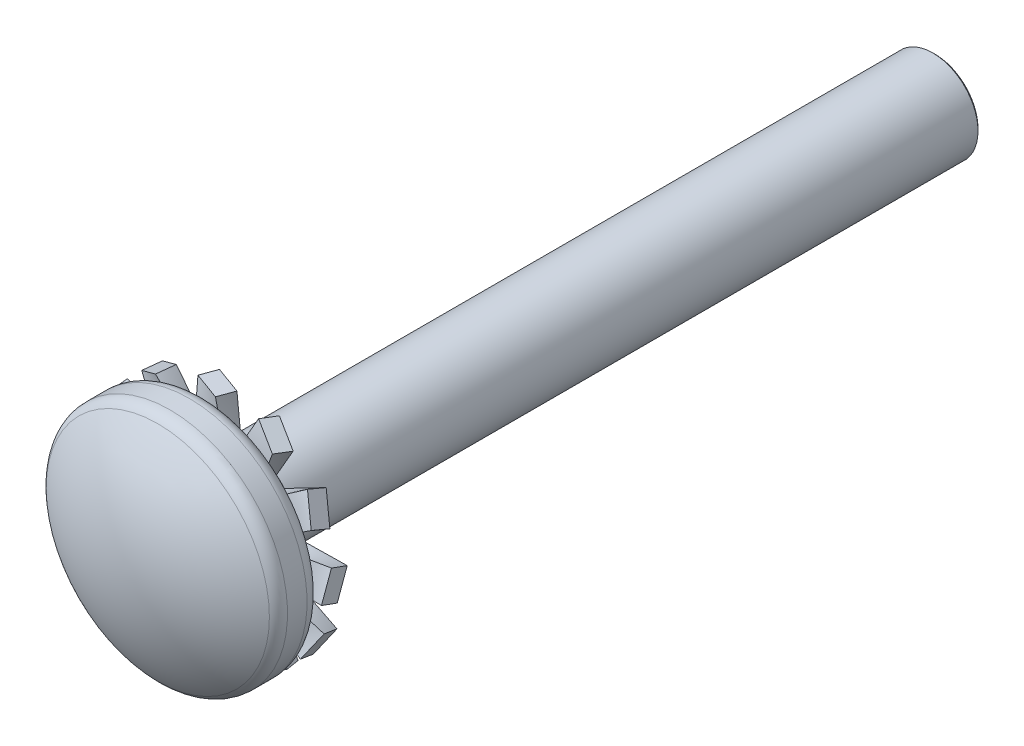
SolidWorks part; units mm, degrees
material "AISI 304"
ref_plane "Front Plane" through (0, 0, 0) normal (0, 0, 1) x (1, 0, 0)
ref_plane "Top Plane" through (0, 0, 0) normal (0, 1, 0) x (1, 0, 0)
ref_plane "Right Plane" through (0, 0, 0) normal (1, 0, 0) x (0, 0, -1)
sketch "Sketch1" plane through (0, 0, 0) normal (0, 0, 1) x (1, 0, 0)
  circle A0 centre (0, 0) radius 2.0828
  dimension "decimal equ" = 4.1656
curve "Helix/Spiral1" pitch 0.7937 height 26.1937 turns 33 parameters "helix length"=26.1937, "pitch"=0.7937
sketch "Sketch2" plane through (0, 0, 0) normal (1, 0, 0) x (0, 0, -1)
  line L0 (0.2977, 2.0828) -> (0.3969, 2.0828)
  line L1 (0.3969, 2.0828) -> (0.6945, 1.5672)
  line L2 (0.2977, 2.0828) -> (0, 1.5672)
  line L3 (0, 1.5672) -> (0.6945, 1.5672)
  line L4 (0.3473, 2.0828) -> (0.3473, 1.5672) construction
  line L6 (0.1488, 1.825) -> (0.5457, 1.825) construction
  line L7 (0, 1.5672) -> (0, 2.0828) construction
  line L8 (0, 2.0828) -> (0, -2.0828) construction
  line L9 (0, 2.0828) -> (0, -2.0828) construction
  point P8 (-3.2742, -2.0828)
  dimension "D1" = 60
  dimension "D3" = 0.0992
  dimension "D4" = 0.3969
  dimension "D2" = 3.2742
sketch "Sketch3" plane through (0, 0, 0) normal (1, 0, 0) x (0, 0, -1)
  line L0 (0, 0) -> (-25.4, 0) construction
  line L1 (0, 1.5672) -> (0.6945, 1.5672) construction
  line L2 (0, 0) -> (-25.4, 0)
  line L3 (0, 0) -> (0, 1.5672)
  line L4 (0, 1.5672) -> (-25.4, 1.5672)
  line L5 (-25.4, 0) -> (-25.4, 1.5672)
  dimension "length" = 25.4
revolve "Revolve1" add sketch "Sketch3" angle 360 about L0
sweep "Sweep1" [suppressed] add profiles "Sketch2" path "Helix/Spiral1"
sketch "Sketch39" plane through (0, 0, 0) normal (0, 0, -1) x (-1, 0, 0)
  circle A0 centre (0, 0) radius 2.0828 construction
  circle A1 centre (0, 0) radius 2.0828
extrude "Extrude5" [suppressed] cut sketch "Sketch39" along normal through all
sketch "Sketch38" plane through (0, 0, 0) normal (0, 0, -1) x (-1, 0, 0)
  circle A2 centre (0, 0) radius 1.4875
  circle A3 centre (0, 0) radius 1.4875
extrude "Extrude6" cut sketch "Sketch38" against normal through all draft 45 flip side to cut
sketch "Sketch10" plane through (0, 0, 0) normal (1, 0, 0) x (0, 0, -1)
  line L0 (0, 0) -> (23.0169, 0) construction
  line L1 (-279.4, 12.7) -> (-25.4, 12.7)
  line L2 (-279.4, 12.7) -> (-279.4, 0)
  line L3 (-279.4, 0) -> (-25.4, 0)
  line L4 (-25.4, 12.7) -> (-25.4, 0)
  line L5 (-25.4, 0) -> (-25.4, 1.5672) construction
  dimension "D1" = 254
  dimension "D2" = 12.7
revolve "Cut-Revolve2" [suppressed] cut sketch "Sketch10" angle 360 about L0
sketch "Sketch41" plane through (0, 0, 0) normal (1, 0, 0) x (0, 0, -1)
  line L0 (-25.4, 2.0828) -> (-25.4, 1.5672)
  line L1 (-25.4, 1.5672) -> (-24.5237, 1.5672)
  line L2 (-24.5237, 1.5672) -> (-24.0081, 2.0828)
  line L3 (-25.4, 2.0828) -> (-24.0081, 2.0828)
  line L4 (0, 1.5672) -> (0.6945, 1.5672) construction
  dimension "D1" = 0.8763
  dimension "D2" = 45
revolve "Cut-Revolve4" [suppressed] cut sketch "Sketch41" angle 360 about L2
sketch "Sketch8" plane through (0, 0, 0) normal (1, 0, 0) x (0, 0, -1)
  line L0 (0, 0) -> (-6.2449, 0) construction
  line L1 (-28.321, 0) -> (-25.4, 0)
  line L2 (-28.321, 0) -> (-28.321, 4.0894)
  line L3 (-28.321, 4.0894) -> (-25.4, 4.0894)
  line L4 (-25.4, 0) -> (-25.4, 4.0894)
  line L5 (-28.321, -4.0894) -> (-25.4, -4.0894) construction
  line L6 (-25.4, 0) -> (-25.4, 1.5672) construction
  dimension "head dia" = 8.1788
  dimension "head height" = 2.921
revolve "Revolve2" add sketch "Sketch8" angle 360 about L0
sketch "Sketch11" plane through (0, 0, 0) normal (1, 0, 0) x (0, 0, -1)
  line L0 (-26.8605, 4.0894) -> (-26.8605, -4.0894) construction
  line L1 (-28.321, 0) -> (-6.8951, 0) construction
  line L2 (-28.321, 4.0894) -> (-25.4, 4.0894) construction
  line L3 (-28.321, 0) -> (-28.321, 4.0894) construction
  line L4 (-26.6049, 4.0894) -> (-25.9258, 4.0894)
  line L6 (-25.4, 0) -> (-25.4, 4.0894) construction
  line L7 (-25.4, 3.5636) -> (-24.765, 3.5636)
  line L8 (-24.765, 3.5636) -> (-24.765, 4.7244)
  line L9 (-24.765, 4.7244) -> (-28.956, 4.7244)
  line L10 (-28.956, 4.7244) -> (-28.956, 0)
  line L11 (-28.956, 0) -> (-28.321, 0)
  arc A0 (-27.0251, 3.8796) -> (-28.321, 0) centre (-21.8656, 0) ccw
  arc A1 (-25.4, 3.5636) -> (-25.9258, 4.0894) centre (-25.9258, 3.5636) ccw
  arc A2 (-27.0251, 3.8796) -> (-26.6049, 4.0894) centre (-26.6049, 3.5636) cw
  dimension "D1" = 0.5258
  dimension "D2" = 0.635
  dimension "D3" = 0.635
  dimension "D4" = 0.635
revolve "Cut-Revolve3" cut sketch "Sketch11" angle 360 about L1
ref_plane "Plane1" through (0, 0, 28.321) normal (0, 0, 1) x (1, 0, 0)
sketch "Sketch12" plane through (0, 0, 28.321) normal (0, 0, 1) x (1, 0, 0)
  line L0 (0.508, 2.3264) -> (0.508, 1.1906)
  line L1 (0.508, 1.1906) -> (1.1906, 0.508) construction
  line L2 (1.1906, 0.508) -> (2.3264, 0.508)
  line L3 (0, 2.3813) -> (0, 0)
  line L4 (0, 0) -> (2.3813, 0)
  line L5 (0, 0) -> (0, 4.0894) construction
  line L6 (0, 0) -> (0.8493, 0.8493) construction
  line L7 (1.1906, 0) -> (1.1906, 1.5633) construction
  line L8 (0.508, 1.1906) -> (0.7079, 0.7079)
  line L9 (1.1906, 0.508) -> (0.7079, 0.7079)
  line L10 (0, 0) -> (0, -1.0114) construction
  line L11 (-0.508, 2.3264) -> (-0.508, 1.1906) construction
  arc A0 (2.3813, 0) -> (2.3264, 0.508) centre (0, 0) ccw
  arc A1 (0.508, 2.3264) -> (0, 2.3813) centre (0, 0) ccw
  arc A2 (-2.3813, 0) -> (-2.3264, 0.508) centre (0, 0) cw construction
  dimension "phillips dia" = 4.7625
  dimension "D2" = 45
  dimension "D4" = 22.5
  dimension "slot width" = 1.016
extrude "Cut-Extrude1" [suppressed] cut sketch "Sketch12" against normal blind 2.4829
draft "Draft3" [suppressed] type of draft neutral plane draft angle 15 neutral plane "Plane1" faces to draft 2 parameters "D1"=15
draft "Draft4" [suppressed] type of draft neutral plane draft angle 5 neutral plane "Plane1" faces to draft 4 parameters "D1"=5
pattern_circular "CirPattern1" [suppressed] count 4 over 360 about axis through (0, 0, 28.321) along (0, 0, -1) of bodies 110
ref_plane "Plane8" through (0, 0, 25.2439) normal (0, 0, -1) x (-1, 0, 0)
sketch "Sketch18" plane through (0, 0, 25.2439) normal (0, 0, 1) x (1, 0, 0)
  line L0 (0, 0) -> (0, 4.064) construction
  line L1 (1.5672, 0) -> (4.064, 0) construction
  circle A0 centre (0, 0) radius 4.064
  circle A1 centre (0, 0) radius 1.5672 construction
  circle A2 centre (0, 0) radius 1.5672 construction
  circle A3 centre (0, 0) radius 2.6908
  circle A4 centre (0, 0) radius 2.0828 construction
  point P8 (2.6908, 0)
  point P10 (0, 2.6908)
  dimension "washer dia." = 8.128
  dimension "D2" = 1.1235
sketch "Sketch21" plane through (0, 0, 25.2439) normal (0, 0, 1) x (1, 0, 0)
  circle A0 centre (0, 0) radius 2.6908
  circle A1 centre (0, 0) radius 1.5672
  circle A2 centre (0, 0) radius 2.0828 construction
extrude "Extrude2" add sketch "Sketch21" against normal blind 0.5842 separate body
ref_plane "Plane9" through (0, 2.6908, 0) normal (0, 1, 0) x (-1, 0, 0)
sketch "Sketch31" plane through (0, 2.6908, 0) normal (0, 1, 0) x (-1, 0, 0)
  line L1 (-0.508, 25.2439) -> (0.508, 25.2439)
  line L2 (-0.508, 25.2439) -> (-0.508, 24.6597)
  line L3 (-0.508, 24.6597) -> (0.508, 24.6597)
  line L4 (0.508, 25.2439) -> (0.508, 24.6597)
  line L5 (-2.6908, 24.6597) -> (2.6908, 24.6597) construction
  line L6 (0, 0) -> (0, 25.2439) construction
  line L7 (0.508, 24.9518) -> (-0.508, 24.9518) construction
  line L8 (0, 25.2439) -> (0, 24.6597) construction
  line L9 (2.6908, 25.2439) -> (-2.6908, 25.2439) construction
  dimension "D1" = 1.016
ref_plane "Plane10" through (0, 4.064, 0) normal (0, 1, 0) x (-1, 0, 0)
sketch "Sketch32" plane through (0, 4.064, 0) normal (0, 1, 0) x (-1, 0, 0)
  line L0 (-0.3775, 25.4) -> (-0.5773, 24.851)
  line L1 (-0.3775, 25.4) -> (0.5773, 25.0525)
  line L2 (-0.5773, 24.851) -> (0.3775, 24.5035)
  line L3 (0.5773, 25.0525) -> (0.3775, 24.5035)
  line L4 (-0.508, 25.2439) -> (-0.508, 24.6597) construction
  line L5 (-0.508, 24.6597) -> (0.508, 24.6597) construction
  line L6 (0.0999, 25.2263) -> (0, 24.9518) construction
  line L7 (0, 24.9518) -> (0.4774, 24.778) construction
  line L8 (0.508, 24.9518) -> (-0.508, 24.9518) construction
  line L9 (0, 0) -> (0, 6.2449) construction
  line L10 (-1.5672, 24.6597) -> (1.5672, 24.6597) construction
  dimension "D1" = 20
sketch "Sketch33" plane through (0, 2.6908, 0) normal (0, 1, 0) x (-1, 0, 0)
  line L1 (1.5672, 25.2439) -> (-1.5672, 25.2439) construction
  line L4 (0.508, 25.2439) -> (-0.508, 25.2439)
  line L5 (0.508, 24.6597) -> (0.508, 25.2439)
  line L6 (-0.508, 24.6597) -> (0.508, 24.6597)
  line L7 (-0.508, 25.2439) -> (-0.508, 24.6597)
  line L8 (0.508, 25.2439) -> (-0.508, 25.2439)
  line L9 (0.508, 24.6597) -> (0.508, 25.2439)
  line L10 (-0.508, 24.6597) -> (0.508, 24.6597)
  line L11 (-0.508, 25.2439) -> (-0.508, 24.6597)
  dimension "D1" = 0
extrude "Extrude3" add sketch "Sketch33" against normal up to next (1.1235 mm away)
loft "Loft2" add profiles "Sketch32", "Sketch31" connector at (0.3775, 4.064, 25.4) connector at (0.508, 2.6908, 25.2439)
pattern_circular "CirPattern4" count 12 over 360 about axis through (0, 0, 24.6597) along (0, 0, 1) of "Loft2", "Extrude3"
sketch "Sketch40" plane through (0, 0, 0) normal (1, 0, 0) x (0, 0, -1)
  line L0 (-25.2439, 4.064) -> (-24.6597, 4.064) construction
  line L1 (-25.2439, -4.064) -> (-24.6597, -4.064) construction
  line L2 (-24.9518, 4.064) -> (-24.9518, -4.064) construction
  line L3 (-24.9518, 0) -> (0, 0) construction
  line L4 (0, -1.4875) -> (0, 1.4875) construction
  line L6 (-25.2439, -5.9931) -> (-25.2439, 5.9931) construction
  dimension "D1" = 0.5842
  dimension "D2" = 8.128
equation "\"D3@Sketch2\" = \"pitch@Helix/Spiral1\"*.125"
equation "\"D4@Sketch2\" = \"pitch@Helix/Spiral1\"*.5"
equation "\"D1@Sketch11\" = \"head height@Sketch8\"*.18"
equation "\"D1@Cut-Extrude1\" = \"head height@Sketch8\"*.85"
equation "\"D1@Sketch31\" = \"washer dia.@Sketch18\"*.125"
equation "\"helix length@Helix/Spiral1\" = \"length@Sketch3\" + \"pitch@Helix/Spiral1\""
equation "\"D1@Sketch38\" = \"pitch@Helix/Spiral1\"*.750"
equation "\"D1@Plane8\" = \"D2@Sketch32\""
equation "\"D2@Sketch18\" = \"D1@Sketch18\"*.45"
equation "\"D2@Sketch2\" = \"pitch@Helix/Spiral1\"*4.125"
equation "\"D1@Sketch40\" = \"washer width@Extrude2\""
equation "\"D2@Sketch40\" = \"washer dia.@Sketch18\""
equation "\"D1@Sketch41\" = \"washer width@Extrude2\"*1.50"
